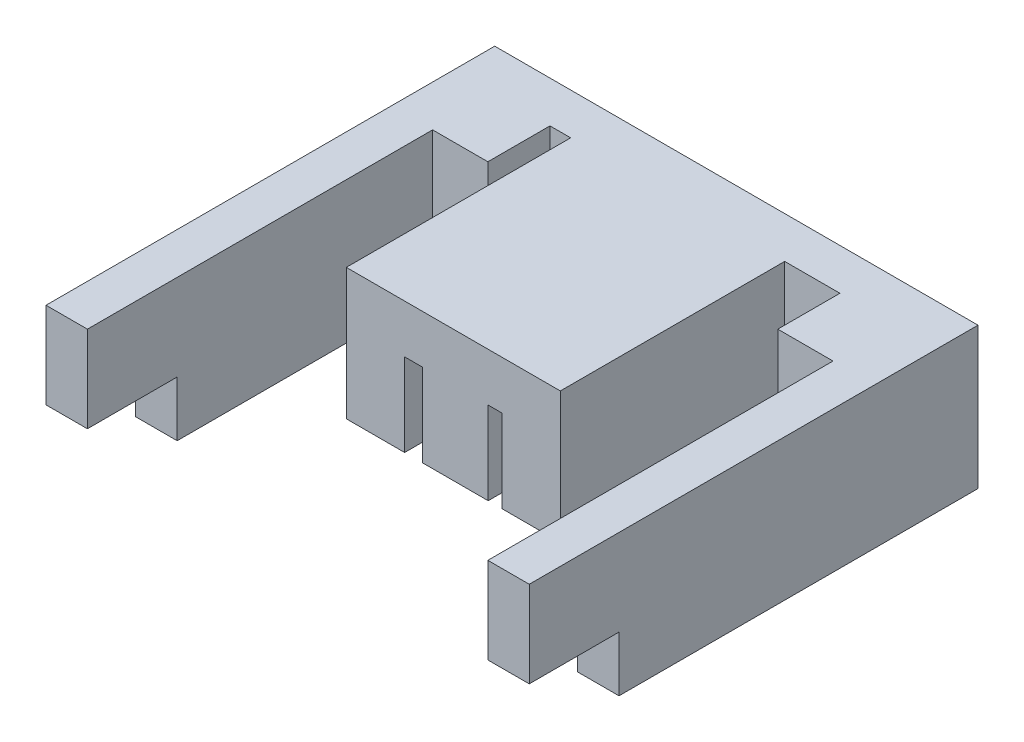
SolidWorks part; units mm, degrees
material "PBT General Purpose"
ref_plane "Front Plane" through (0, 0, 0) normal (0, 0, 1) x (1, 0, 0)
ref_plane "Top Plane" through (0, 0, 0) normal (0, 1, 0) x (1, 0, 0)
ref_plane "Right Plane" through (0, 0, 0) normal (1, 0, 0) x (0, 0, -1)
sketch "Sketch1" plane through (0, 0, 0) normal (0, 1, 0) x (1, 0, 0)
  line L0 (29, -32.5) -> (35, -32.5)
  line L1 (-35, 32.5) -> (35, 32.5)
  line L2 (-35, 32.5) -> (-35, -32.5)
  line L3 (-35, -32.5) -> (-29, -32.5)
  line L4 (35, 32.5) -> (35, -32.5)
  line L5 (-29, 26.5) -> (29, 26.5)
  line L6 (-29, 26.5) -> (-29, -32.5)
  line L8 (29, 26.5) -> (29, -32.5)
  point P8 (0, 26.5)
  point P10 (-35, 0)
  dimension "D1" = 70
  dimension "D2" = 65
  dimension "D3" = 6
  dimension "D4" = 6
  dimension "D5" = 6
extrude "Boss-Extrude1" add sketch "Sketch1" along normal blind 20.5
sketch "Sketch2" plane through (0, 0, 0) normal (0, -1, 0) x (1, 0, 0)
  line L0 (35, 32.5) -> (35, -32.5) construction
  line L1 (29, 32.5) -> (35, 32.5)
  line L2 (29, 32.5) -> (29, 19.5)
  line L3 (29, 19.5) -> (35, 19.5)
  line L4 (35, 32.5) -> (35, 19.5)
  line L5 (0, -1000) -> (0, 49000) construction
  line L6 (-29, -26.5) -> (29, -26.5) construction
  line L7 (-12.5, -26.5) -> (12.5, -26.5)
  line L8 (-12.5, -26.5) -> (-12.5, -32.5)
  line L9 (-12.5, -32.5) -> (12.5, -32.5)
  line L10 (12.5, -26.5) -> (12.5, -32.5)
  line L11 (35, -32.5) -> (-35, -32.5) construction
  line L12 (-29, 19.5) -> (-35, 19.5)
  line L13 (-35, 32.5) -> (-35, 19.5)
  line L14 (-29, 32.5) -> (-35, 32.5)
  line L15 (-29, 32.5) -> (-29, 19.5)
  point P18 (0, -26.5)
  point P19 (0, -26.5)
  dimension "D1" = 13
  dimension "D2" = 25
extrude "Cut-Extrude1" cut sketch "Sketch2" against normal blind 8
sketch "Sketch3" plane through (0, 20.5, 0) normal (0, 1, 0) x (1, 0, 0)
  line L0 (-29, -32.5) -> (-29, 26.5) construction
  line L1 (-14, 21) -> (9, 21)
  line L2 (-14, 21) -> (-14, -2)
  line L3 (-14, -2) -> (9, -2)
  line L4 (9, 21) -> (9, -2)
  line L5 (-29, 26.5) -> (29, 26.5) construction
  dimension "D1" = 23
  dimension "D2" = 23
  dimension "D3" = 15
  dimension "D4" = 5.5
extrude "Boss-Extrude2" add sketch "Sketch3" against normal offset from surface (7 mm away) 13.5 separate body up to face at (-25.5, 0, -13.1667)
sketch "Sketch4" plane through (0, 20.5, 0) normal (0, 1, 0) x (1, 0, 0)
  line L0 (-18, 26.5) -> (-18, -6)
  line L1 (-29, 26.5) -> (29, 26.5) construction
  line L2 (-18, -6) -> (13, -6)
  line L3 (13, -6) -> (13, 26.5)
  line L4 (-14, 21) -> (-14, -2)
  line L5 (-14, -2) -> (9, -2)
  line L6 (9, -2) -> (9, 21)
  line L7 (9, 21) -> (-14, 21)
  line L8 (-14, 21) -> (-14, -2)
  line L9 (-14, -2) -> (9, -2)
  line L10 (9, -2) -> (9, 21)
  line L11 (9, 21) -> (-14, 21)
  line L12 (13, 26.5) -> (-18, 26.5)
  line M12 (-29, 26.5) -> (29, 26.5)
  dimension "D2" = 4
  dimension "D3" = 4
  dimension "D4" = 4
  dimension "D1" = 0
extrude "Boss-Extrude4" add sketch "Sketch4" against normal offset from surface (19 mm away) 12 contours L2 L3 L0 L11 L10 L9 L8 M12 region at (-2.5, 20.5, -26.0509) up to face at (-2.5, 13.5, -9.5) offset beyond the face yes
sketch "Sketch5" plane through (0, 1.5, 0) normal (0, -1, 0) x (1, 0, 0)
  line L0 (-14, -21) -> (9, -21) construction
  line L1 (-6.95, -21) -> (-9.55, -21)
  line L2 (-6.95, -21) -> (-6.95, -26.5)
  line L3 (-6.95, -26.5) -> (-9.55, -26.5)
  line L4 (-9.55, -21) -> (-9.55, -26.5)
  line L5 (12.5, -26.5) -> (-12.5, -26.5) construction
  line L6 (9, 2) -> (-14, 2) construction
  line L7 (-9.55, 2) -> (-6.95, 2)
  line L8 (-9.55, 2) -> (-9.55, 6)
  line L9 (-9.55, 6) -> (-6.95, 6)
  line L10 (-6.95, 2) -> (-6.95, 6)
  line L11 (13, 6) -> (-18, 6) construction
  line L12 (-18, 6) -> (-18, -26.5) construction
  line L13 (-18, 2) -> (-14, 2)
  line L14 (-18, 2) -> (-18, -13)
  line L15 (-18, -13) -> (-14, -13)
  line L16 (-14, 2) -> (-14, -13)
  line L17 (-14, 2) -> (-14, -21) construction
  line L18 (9, 2) -> (-14, 2) construction
  line L19 (2.55, 6) -> (4.55, 6)
  line L20 (2.55, 6) -> (2.55, 2)
  line L21 (2.55, 2) -> (4.55, 2)
  line L22 (4.55, 6) -> (4.55, 2)
  line L23 (-14, 2) -> (-14, -21) construction
  dimension "D1" = 2
  dimension "D2" = 9.5
  dimension "D3" = 15
  dimension "D4" = 2.6
  dimension "D5" = 4.45
extrude "Cut-Extrude2" cut sketch "Sketch5" against normal up to surface (12 mm away) up to face at (-2.5, 13.5, -9.5)
sketch "Sketch7" plane through (0, 20.5, 0) normal (0, 1, 0) x (1, 0, 0)
  line L1 (29, 26.5) -> (21, 26.5)
  line L2 (29, 26.5) -> (29, 17.5)
  line L3 (29, 17.5) -> (21, 17.5)
  line L4 (21, 26.5) -> (21, 17.5)
  line L5 (-29, 26.5) -> (-21, 26.5)
  line L6 (-29, 26.5) -> (-29, 17.5)
  line L7 (-29, 17.5) -> (-21, 17.5)
  line L8 (-21, 26.5) -> (-21, 17.5)
  dimension "D1" = 8
  dimension "D2" = 9
  dimension "D3" = 9
  dimension "D4" = 8
extrude "Boss-Extrude5" add sketch "Sketch7" against normal up to surface (20.5 mm away) up to face at (25.5, 0, -13.1667)
sketch "Sketch8" plane through (0, 0, -32.5) normal (0, 0, -1) x (-1, 0, 0)
  line L0 (-35, 20.5) -> (-35, 0) construction
  line L1 (35, 20.5) -> (35, 0) construction
  line L2 (12.5, 0) -> (35, 0) construction
  line L3 (-35, 0) -> (-12.5, 0) construction
  circle A0 centre (-25, 11) radius 2
  circle A1 centre (25, 11) radius 2
  dimension "D1" = 4
  dimension "D2" = 4
  dimension "D5" = 11
  dimension "D6" = 11
  dimension "D3" = 10
  dimension "D4" = 10
extrude "Cut-Extrude4" cut sketch "Sketch8" against normal blind 10
equation "\"body_height\"= 41mm"
equation "\"D1@Boss-Extrude1\"=\"body_height\" / 2"
equation "\"D1@Boss-Extrude2\"=12+1.5"
